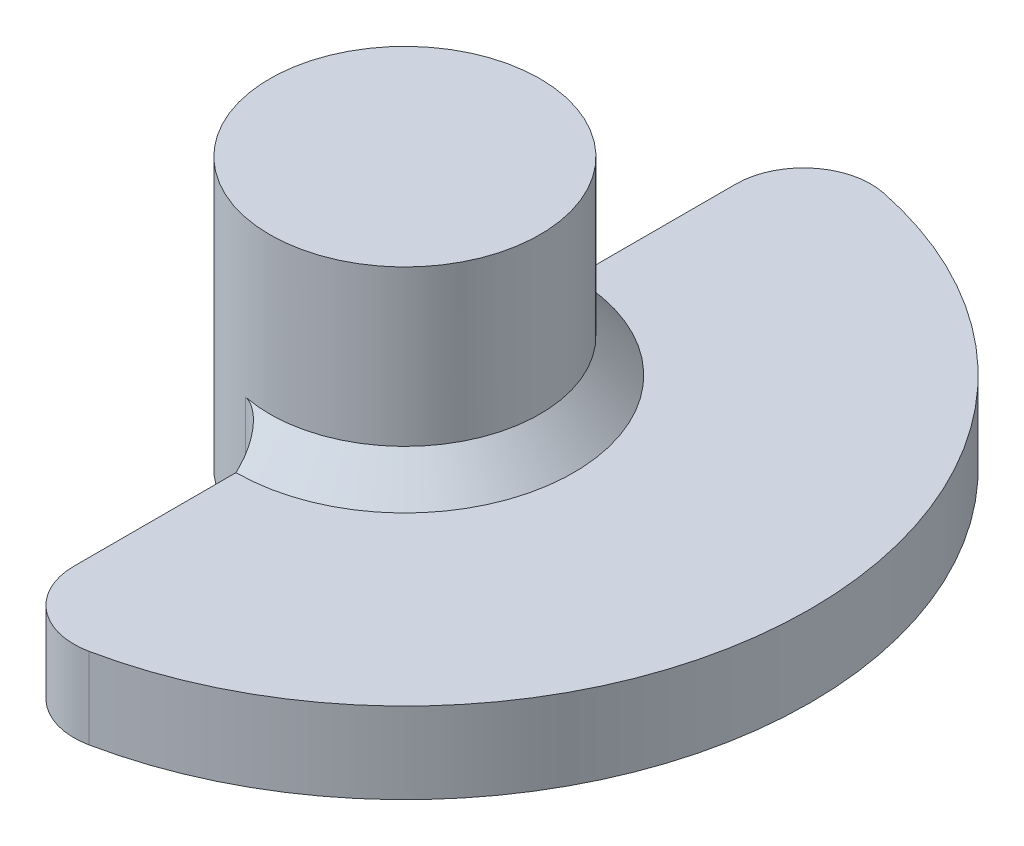
SolidWorks part; units mm, degrees
ref_plane "Plano frontal" through (0, 0, 0) normal (0, 0, 1) x (1, 0, 0)
ref_plane "Plano superior" through (0, 0, 0) normal (0, 1, 0) x (1, 0, 0)
ref_plane "Plano direito" through (0, 0, 0) normal (1, 0, 0) x (0, 0, -1)
sketch "Esboço1" plane through (0, 0, 0) normal (0, 1, 0) x (1, 0, 0)
  line L0 (0, 6) -> (0, -6)
  arc A0 (0, -6) -> (0, 6) centre (0, 0) ccw
  dimension "D1" = 12
extrude "Ressalto-extrusão1" add sketch "Esboço1" along normal blind 1.2
sketch "Esboço3" plane through (0, 0, 0) normal (0, -1, 0) x (1, 0, 0)
  circle A0 centre (0, 0) radius 2
  dimension "D1" = 4
extrude "Ressalto-extrusão2" add sketch "Esboço3" against normal blind 4
fillet "Filete1" radius 1 1 edges at (0, 0.6, 6) type face fillet first side face at (0, 0.6, 4) second side face at (3, 0.6, 0)
fillet "Filete2" radius 1 1 edges at (0, 0.6, -6) type face fillet first side face at (0, 0.6, -4) second side face at (3.2848, 0.6, -0.3318)
fillet "Filete3" radius 0.5 1 edges at (0, 0.6, -2) type face fillet first side face at (0, 0.6, -3.4495) second side face at (0, 4, -2)
fillet "Filete4" radius 0.5 1 edges at (0, 0.6, 2) type face fillet first side face at (0, 0.6, 3.4495) second side face at (0, 4, -2)
chamfer "Chanfro1" distance 0.5 angle 45 1 edges at (2, 1.2, 0)
